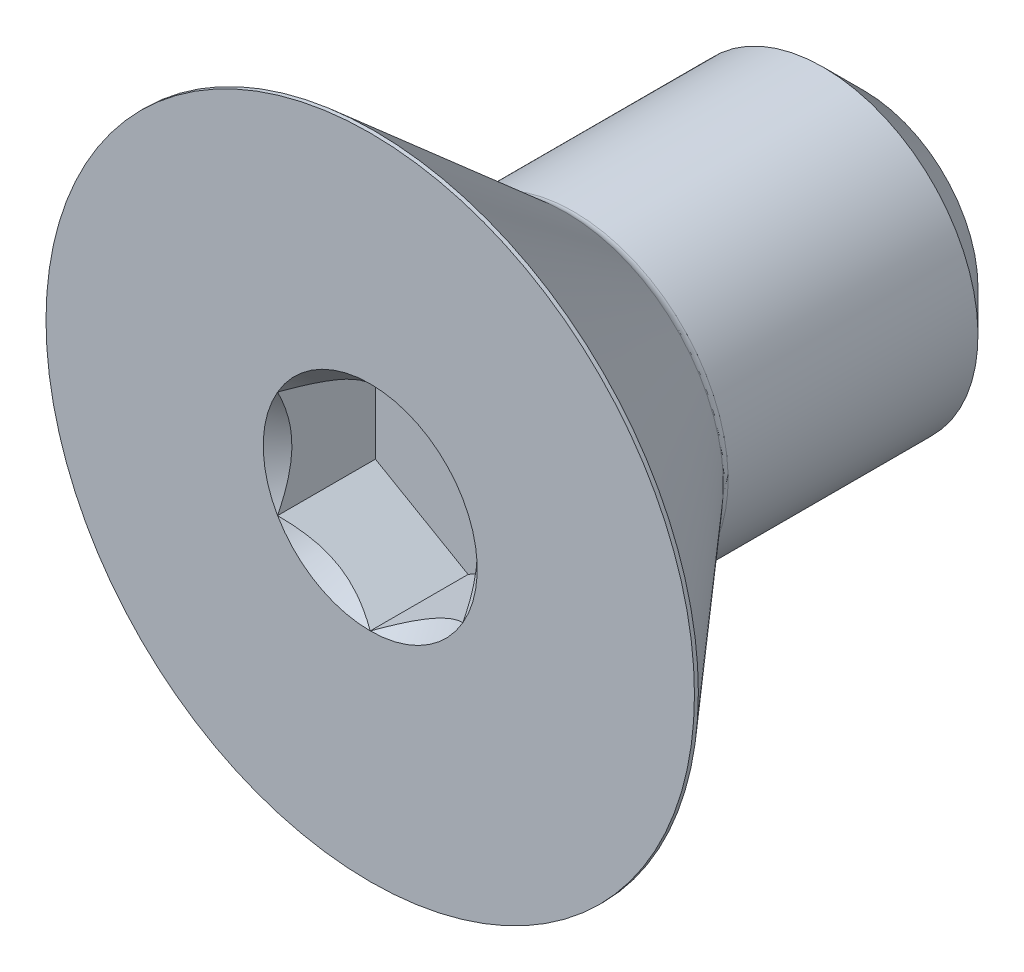
SolidWorks part; units mm, degrees
material "Plain Carbon Steel"
ref_plane "Front Plane" through (0, 0, 0) normal (0, 0, 1) x (1, 0, 0)
ref_plane "Top Plane" through (0, 0, 0) normal (0, 1, 0) x (1, 0, 0)
ref_plane "Right Plane" through (0, 0, 0) normal (1, 0, 0) x (0, 0, -1)
sketch "Sketch1" plane through (0, 0, 0) normal (1, 0, 0) x (0, 0, -1)
  line L0 (-6.35, 0) -> (6.35, 0) construction
  line L1 (-6.35, 0) -> (-6.35, 8.3312)
  line L2 (-6.35, 8.3312) -> (-6.2494, 8.3312)
  line L3 (-6.2494, 8.3312) -> (-1.3208, 4.0468)
  line L4 (-6.2494, -8.3312) -> (-1.3208, -4.0468)
  line L5 (6.35, 0) -> (6.35, 3.9751)
  line L6 (6.35, 3.9751) -> (-1.3208, 3.9751)
  line L7 (5.2917, 3.9751) -> (6.35, 2.9168)
  line L8 (6.2618, 4.1279) -> (6.9674, 2.9058) construction
  line L9 (6.9674, 2.9058) -> (7.6729, 4.1279) construction
  line L10 (7.6729, 4.1279) -> (6.2618, 4.1279) construction
  line L11 (6.3059, 4.0515) -> (7.6288, 4.0515)
  line L12 (7.6288, 4.0515) -> (7.0556, 3.0586)
  line L13 (7.0556, 3.0586) -> (6.8792, 3.0586)
  line L14 (6.8792, 3.0586) -> (6.3059, 4.0515)
  line L15 (6.9674, 3.0586) -> (6.9674, 2.9058) construction
  line L16 (6.35, 3.9751) -> (7.5847, 3.9751) construction
  line L17 (6.9674, 4.1279) -> (6.9674, 3.9751) construction
  line L18 (6.35, -3.9751) -> (-1.3208, -3.9751)
  arc A0 (-1.3208, 4.0468) -> (-1.129, 3.9751) centre (-1.129, 4.2675) ccw
  point P2 (0, 0)
  point P23 (-3.8354, 0)
  point P27 (6.9674, 4.0515)
  point P30 (4.2333, -3.9751)
  point P31 (-1.3208, 8.3312)
  point P34 (-6.2494, -8.3312)
  dimension "Length" = 12.7
  dimension "Head Height" = 5.0292
  dimension "Head Diameter" = 16.6624
  dimension "Countersink Angle" = 82
  dimension "Screw Size Decimal Equivalent" = 7.9502
  dimension "Pitch" = 1.4111
  dimension "D4" = 0.1764
  dimension "D3" = 45
  dimension "D5" = 1.0583
  dimension "D6" = 2.5146
  dimension "D1" = 2.1167
  dimension "D7" = 0.1006
sketch "Sketch8" plane through (0, 0, 0) normal (0, 0, 1) x (1, 0, 0)
  line L1 (0, 2.7496) -> (-2.3812, 1.3748)
  line L2 (-2.3812, 1.3748) -> (-2.3812, -1.3748)
  line L3 (-2.3812, -1.3748) -> (0, -2.7496)
  line L4 (0, -2.7496) -> (2.3812, -1.3748)
  line L5 (2.3812, -1.3748) -> (2.3812, 1.3748)
  line L6 (2.3812, 1.3748) -> (0, 2.7496)
  circle A0 centre (0, 0) radius 2.3812 construction
  dimension "Drive Size" = 4.7625
sketch "Sketch2" plane through (0, 0, 0) normal (1, 0, 0) x (0, 0, -1)
  line L0 (-6.2494, 8.3312) -> (-1.3208, 4.0468) construction
  line L1 (-6.35, 0) -> (-6.35, 8.3312) construction
  line L2 (-6.2494, 8.3312) -> (-1.3208, 4.0468)
  line L3 (-6.35, 0) -> (-6.35, 8.3312)
  line L4 (-6.35, 8.3312) -> (-6.2494, 8.3312) construction
  line L5 (-6.35, 8.3312) -> (-6.2494, 8.3312)
  line L6 (-1.129, 3.9751) -> (5.2917, 3.9751)
  line L7 (5.2917, 3.9751) -> (6.35, 2.9168)
  line L8 (6.35, 2.9168) -> (6.35, 0)
  line L9 (6.35, 0) -> (-6.35, 0)
  arc A0 (-1.3208, 4.0468) -> (-1.129, 3.9751) centre (-1.129, 4.2675) ccw construction
  arc A1 (-1.3208, 4.0468) -> (-1.129, 3.9751) centre (-1.129, 4.2675) ccw
revolve "Revolve1" add sketch "Sketch2" angle 360 about L9
sketch "Sketch9" plane through (0, 0, 6.35) normal (0, 0, 1) x (1, 0, 0)
  line L0 (2.3812, -1.3748) -> (2.3812, 1.3748) construction
  line L1 (0, -2.7496) -> (2.3812, -1.3748) construction
  line L2 (-2.3812, -1.3748) -> (0, -2.7496) construction
  line L3 (-2.3812, 1.3748) -> (-2.3812, -1.3748) construction
  line L4 (0, 2.7496) -> (-2.3812, 1.3748) construction
  line L5 (2.3812, 1.3748) -> (0, 2.7496) construction
  line L6 (2.3812, -1.3748) -> (2.3812, 1.3748)
  line L7 (0, -2.7496) -> (2.3812, -1.3748)
  line L8 (-2.3812, -1.3748) -> (0, -2.7496)
  line L9 (-2.3812, 1.3748) -> (-2.3812, -1.3748)
  line L10 (0, 2.7496) -> (-2.3812, 1.3748)
  line L11 (2.3812, 1.3748) -> (0, 2.7496)
sketch "Sketch10" plane through (0, 0, 6.35) normal (0, 0, 1) x (1, 0, 0)
  circle A0 centre (0, 0) radius 2.7496
extrude "Cut-Extrude2" cut sketch "Sketch10" against normal up to vertex (2.5146 mm away) draft 45 up to point (0, 0, 3.8354)
extrude "Cut-Extrude1" cut sketch "Sketch9" against normal up to vertex (2.5146 mm away) up to point (0, 0, 3.8354)
ref_plane "Plane1" [suppressed] through (0, 0, 1.129) normal (0, 0, 1) x (1, 0, 0)
split "Split1" [suppressed] bodies to split 111
sketch "Sketch3" [suppressed] plane through (0, 0, -6.35) normal (0, 0, -1) x (-1, 0, 0)
  circle A0 centre (0, 0) radius 3.9751 construction
  circle A1 centre (0, 0) radius 3.9751
curve "Helix/Spiral1" [suppressed] pitch 1.4111 height 12.7 turns 9
sketch "Sketch4" [suppressed] plane through (0, 0, 0) normal (1, 0, 0) x (0, 0, -1)
  line L0 (6.3059, 4.0515) -> (7.6288, 4.0515) construction
  line L1 (6.8792, 3.0586) -> (6.3059, 4.0515) construction
  line L2 (7.0556, 3.0586) -> (6.8792, 3.0586) construction
  line L3 (7.6288, 4.0515) -> (7.0556, 3.0586) construction
  line L4 (6.3059, 4.0515) -> (7.6288, 4.0515)
  line L5 (6.8792, 3.0586) -> (6.3059, 4.0515)
  line L6 (7.0556, 3.0586) -> (6.8792, 3.0586)
  line L7 (7.6288, 4.0515) -> (7.0556, 3.0586)
sweep "Cut-Sweep1" [suppressed] cut profiles "Sketch4" path "Helix/Spiral1"
sketch "Sketch7" [suppressed] plane through (0, 0, 1.129) normal (0, 0, 1) x (1, 0, 0)
  circle A0 centre (0, 0) radius 3.9751
extrude "Boss-Extrude2" [suppressed] add sketch "Sketch7" against normal up to next draft 20
equation "\"D4@Sketch1\" = \"Pitch@Sketch1\" / 8"
equation "\"D5@Sketch1\"=\"Pitch@Sketch1\"*0.75"
equation "\"D4@Helix/Spiral1\"=\"Pitch@Sketch1\""
equation "\"D3@Helix/Spiral1\"=\"Length@Sketch1\""
equation "\"D6@Sketch1\"=\"Head Height@Sketch1\"/2"
equation "\"D1@Sketch1\"=\"Pitch@Sketch1\"*1.5"
equation "\"D7@Sketch1\"=\"Head Height@Sketch1\"*0.02"
